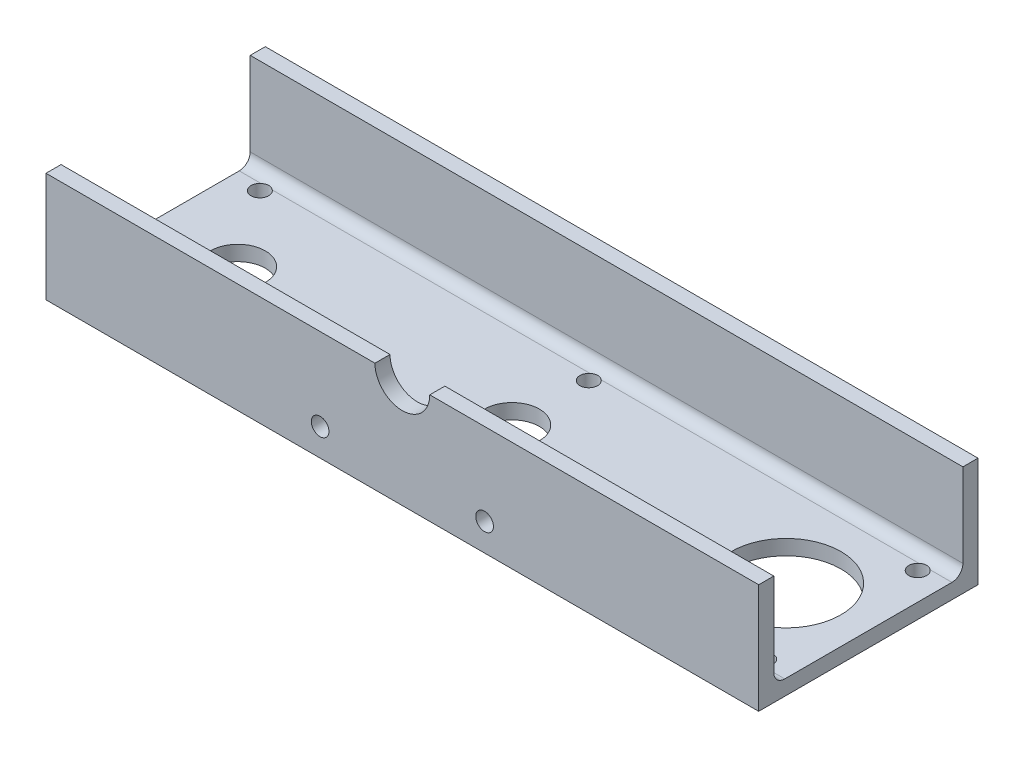
SolidWorks part; units mm, degrees
ref_plane "Front Plane" through (0, 0, 0) normal (0, 0, 1) x (1, 0, 0)
ref_plane "Top Plane" through (0, 0, 0) normal (0, 1, 0) x (1, 0, 0)
ref_plane "Right Plane" through (0, 0, 0) normal (1, 0, 0) x (0, 0, -1)
sketch "Sketch1" plane through (0, 0, 0) normal (1, 0, 0) x (0, 0, -1)
  line L0 (-21.9075, 9.2075) -> (21.9075, 9.2075)
  line L1 (-25.4, -12.7) -> (25.4, -12.7)
  line L2 (-25.4, -12.7) -> (-25.4, 12.7)
  line L3 (-25.4, 12.7) -> (25.4, 12.7)
  line L4 (25.4, -12.7) -> (25.4, 12.7)
  line L5 (-25.4, -12.7) -> (25.4, 12.7) construction
  line L6 (-25.4, 12.7) -> (25.4, -12.7) construction
  line L7 (21.9075, -6.6675) -> (21.9075, 9.2075)
  line L8 (-19.3675, -9.2075) -> (19.3675, -9.2075)
  line L9 (-21.9075, -6.6675) -> (-21.9075, 9.2075)
  line L10 (-21.9075, 9.2075) -> (-21.9075, 12.7)
  line L11 (21.9075, 9.2075) -> (21.9075, 12.7)
  line L12 (21.9075, -9.2075) -> (21.9075, 9.2075) construction
  line L13 (-21.9075, -9.2075) -> (21.9075, -9.2075) construction
  line L14 (-21.9075, -9.2075) -> (-21.9075, 9.2075) construction
  arc A0 (21.9075, -6.6675) -> (19.3675, -9.2075) centre (19.3675, -6.6675) cw
  arc A1 (-19.3675, -9.2075) -> (-21.9075, -6.6675) centre (-19.3675, -6.6675) cw
  point P0 (0, 0)
  dimension "D4" = 2.54
  dimension "D1" = 25.4
  dimension "D2" = 50.8
  dimension "D3" = 3.4925
extrude "Boss-Extrude1" add sketch "Sketch1" against normal blind 165.1 contours L8 A1 L9 L10 L3 L2 L1 L4 L11 L7 A0 region at (0, 1.27, 22.4755)
sketch "Sketch2" plane through (0, -12.7, 0) normal (0, -1, 0) x (1, 0, 0)
  circle A2 centre (-19.05, 0) radius 12.7
  dimension "D1" = 25.4
extrude "Cut-Extrude1" cut sketch "Sketch2" against normal blind 11.938
sketch "Sketch3" plane through (0, 0, 25.4) normal (0, 0, 1) x (1, 0, 0)
  line L0 (-165.1, 12.7) -> (0, 12.7)
  line L4 (-75.6156, 51.5798) -> (-89.55, 51.5798)
  line L5 (-89.5172, 49.2213) -> (-75.5828, 49.2139)
  line L6 (-75.55, 51.5798) -> (-89.4844, 51.5798)
  line L7 (-89.4844, 49.2176) -> (-75.55, 49.2176)
  line L8 (-82.55, 49.2176) -> (-82.55, -12.7)
  line L9 (-165.1, -12.7) -> (0, -12.7) construction
  line L10 (-165.1, 12.7) -> (0, 12.7) construction
  circle A0 centre (-82.55, 12.7) radius 6.35
  dimension "D1" = 12.7
extrude "Cut-Extrude2" cut sketch "Sketch3" against normal blind 9.398 contours L0 A0 L8 | L8 A0 L0 region at (-85.245, 10.005, 25.4) region at (-79.855, 10.005, 25.4)
sketch "Sketch4" plane through (0, -12.7, 0) normal (0, -1, 0) x (1, 0, 0)
  circle A2 centre (-82.55, 0) radius 6.35
  circle A3 centre (-146.05, 0) radius 6.35
extrude "Cut-Extrude3" cut sketch "Sketch4" against normal blind 6.35
sketch "Sketch5" plane through (0, -12.7, 0) normal (0, -1, 0) x (1, 0, 0)
  circle A6 centre (-6.35, -17.78) radius 2.05
  circle A7 centre (-6.35, 17.78) radius 2.05
  circle A8 centre (-82.55, 17.78) radius 2.05
  circle A9 centre (-82.55, -17.78) radius 2.05
  circle A10 centre (-158.75, 17.78) radius 2.05
  circle A11 centre (-158.75, -17.78) radius 2.05
extrude "Cut-Extrude4" cut sketch "Sketch5" against normal blind 6.35
sketch "Sketch6" plane through (0, 0, 25.4) normal (0, 0, 1) x (1, 0, 0)
  circle A2 centre (-101.6, -6.35) radius 2.05
  circle A3 centre (-63.5, -6.35) radius 2.05
extrude "Cut-Extrude5" cut sketch "Sketch6" against normal blind 6.35
